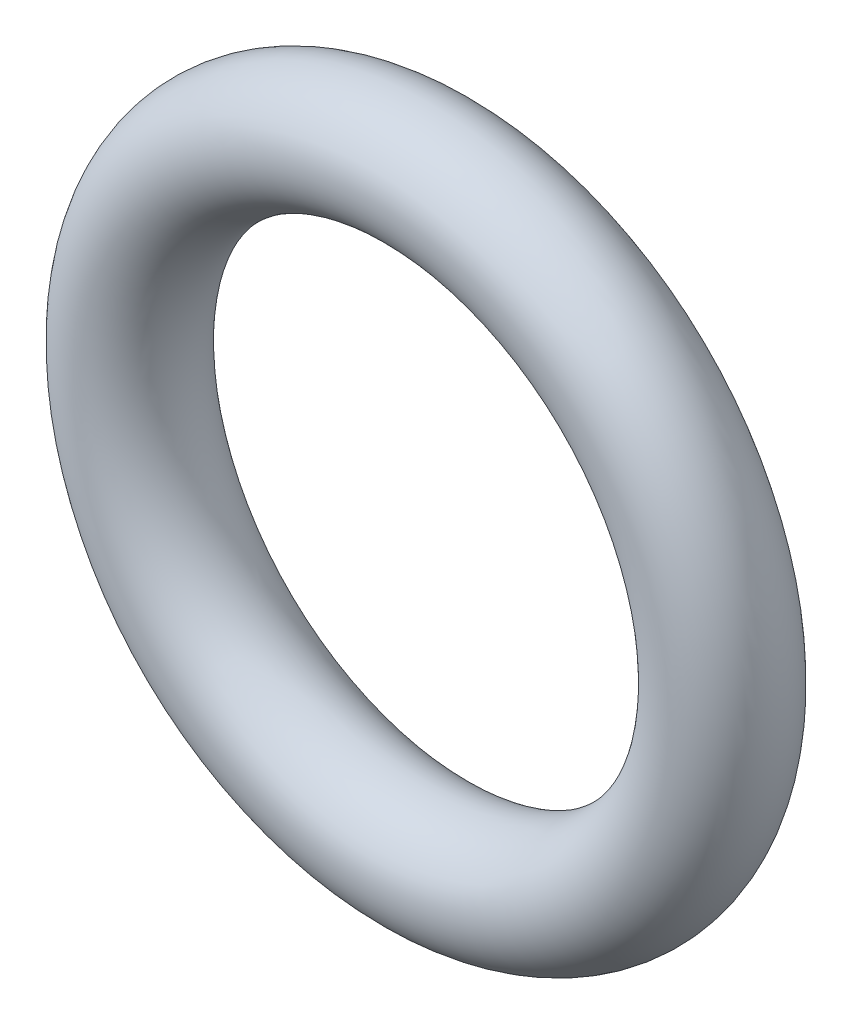
SolidWorks part; units mm, degrees
ref_plane "Front Plane" through (0, 0, 0) normal (0, 0, 1) x (1, 0, 0)
ref_plane "Top Plane" through (0, 0, 0) normal (0, 1, 0) x (1, 0, 0)
ref_plane "Right Plane" through (0, 0, 0) normal (1, 0, 0) x (0, 0, -1)
sketch "Sketch1" plane through (0, 0, 0) normal (1, 0, 0) x (0, 0, -1)
  circle A0 centre (0, 0) radius 1.6867
  dimension "D1" = 3.3734
sketch "Sketch2" plane through (0, 0, 0) normal (0, 0, 1) x (1, 0, 0)
  circle A0 centre (0, -8.4336) radius 8.4336
  dimension "D1" = 16.8672
sweep "Sweep1" add profiles "Sketch1" path "Sketch2"
ref_point "Point1" parameters "D1"=0.762
sketch "Sketch3" plane through (0, 0, 0) normal (0, 0, 1) x (1, 0, 0)
  line L0 (0, -1.6867) -> (0, -15.1805) construction
  circle A0 centre (0, -8.4336) radius 6.7469 construction
  circle A1 centre (0, -8.4336) radius 6.7469
  point P3 (-4.7625, -3.6546)
  point P4 (4.7625, -3.6546)
  point P5 (4.7625, -13.2126)
  point P6 (-4.7625, -13.2126)
  dimension "D1" = 9.525
  dimension "D2" = 9.525
ref_point "Point2"
ref_point "Point3"
ref_point "Point4"
ref_point "Point5"
sketch "Sketch4" plane through (0, 0, 0) normal (1, 0, 0) x (0, 0, -1)
  point P0 (1.6294, -17.2048)
ref_point "Point6"
